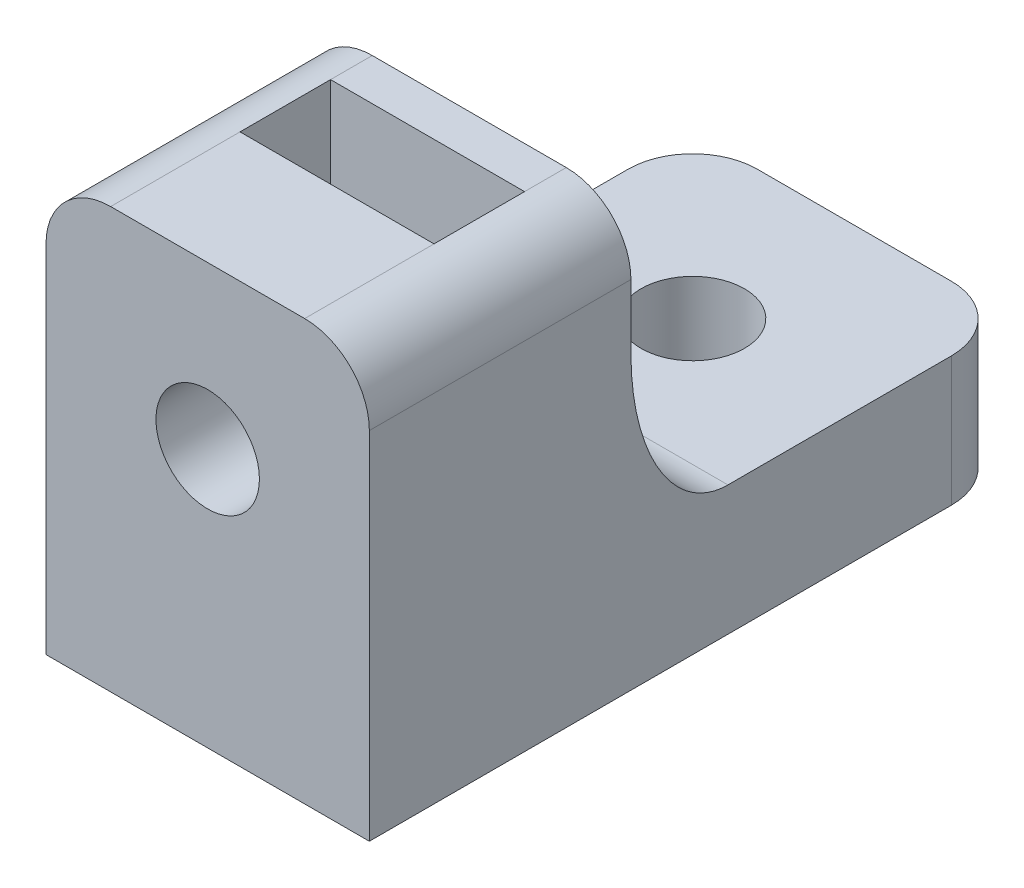
SolidWorks part; units mm, degrees
material "PET-G"
ref_plane "Front Plane" through (0, 0, 0) normal (0, 0, 1) x (1, 0, 0)
ref_plane "Top Plane" through (0, 0, 0) normal (0, 1, 0) x (1, 0, 0)
ref_plane "Right Plane" through (0, 0, 0) normal (1, 0, 0) x (0, 0, -1)
sketch "Sketch1" plane through (0, 0, 0) normal (0, 1, 0) x (1, 0, 0)
  line L0 (5, 8.09) -> (-5, 8.09)
  line L1 (-5, 0) -> (5, 0)
  line L2 (-5, 0) -> (-5, 20)
  line L3 (-5, 20) -> (5, 20)
  line L4 (5, 0) -> (5, 20)
  line L6 (3, 6.8) -> (-3, 6.8)
  line L7 (3, 6.8) -> (3, 4)
  line L8 (3, 4) -> (-3, 4)
  line L9 (-3, 6.8) -> (-3, 4)
  line L10 (3, 6.8) -> (-3, 4) construction
  line L11 (3, 4) -> (-3, 6.8) construction
  point P7 (0, 5.4)
  dimension "D1" = 10
  dimension "D2" = 20
  dimension "D3" = 2.8
  dimension "D4" = 4
  dimension "D5" = 6
extrude "Base" add sketch "Sketch1" along normal blind 4 contours L3 L4 L1 L2
extrude "VerticalPiece" add sketch "Sketch1<3>" along normal blind 13 contours L1 L4 L0 L2 L9 L6 L7 L8 region at (0, 0, -3.6898)
sketch "Sketch1<3>" plane through (0, 0, 0) normal (0, 1, 0) x (1, 0, 0) same geometry as "Sketch1"
fillet "FilletCorner" radius 3 1 edges at (0, 4, -8.09) second distance 5 first distance on face at (0, 4, -14.045)
hole_wizard "Ø3.2 (3.2) Horizontal Hole" positions "Sketch2" profile "Sketch4" hole size "Ø3.2" standard "ANSI Metric" end condition through all
sketch "Sketch2" plane through (0, 0, 0) normal (0, -1, 0) x (-1, 0, 0)
  line L0 (5, 0) -> (-5, 0) construction
  point P0 (0, 15)
  dimension "D1" = 15
sketch "Sketch4" plane through (0, 0, -15) normal (1, 0, 0) x (0, 0, -1)
  line L0 (0, 0) -> (0, 13)
  line L1 (0, 13) -> (1.6, 13)
  line L2 (1.6, 13) -> (1.6, 0)
  line L5 (1.6, 0) -> (0, 0)
  line L11 (0, -6.35) -> (0, 107.95) construction
  dimension "Thru Hole Dia." = 3.2
  dimension "Thru Hole Depth" = 13
hole_wizard "Ø3.2 (3.2) Vertical Hole" positions "Sketch5" profile "Sketch6" hole size "Ø3.2" standard "ANSI Metric" end condition through all
sketch "Sketch5" plane through (0, 0, 0) normal (0, 0, 1) x (1, 0, 0)
  line L0 (-5, 0) -> (5, 0) construction
  point P0 (0, 8)
  dimension "D1" = 8
sketch "Sketch6" plane through (0, 8, 0) normal (1, 0, 0) x (0, -1, 0)
  line L0 (0, 0) -> (0, 20)
  line L1 (0, 20) -> (1.6, 20)
  line L2 (1.6, 20) -> (1.6, 0)
  line L5 (1.6, 0) -> (0, 0)
  line L11 (0, -6.35) -> (0, 107.95) construction
  dimension "Thru Hole Dia." = 3.2
  dimension "Thru Hole Depth" = 20
extrude "NutSlot" add sketch "Sketch1<4>" along normal blind 4.8 contours L6 L9 L8 L7 region at (0, 0, -5.4)
sketch "Sketch1<4>" plane through (0, 0, 0) normal (0, 1, 0) x (1, 0, 0) same geometry as "Sketch1"
fillet "Fillet2" radius 2 4 edges at (5, 2, -20) (-5, 2, -20) (-5, 13, -4.045) (5, 13, -4.045)
